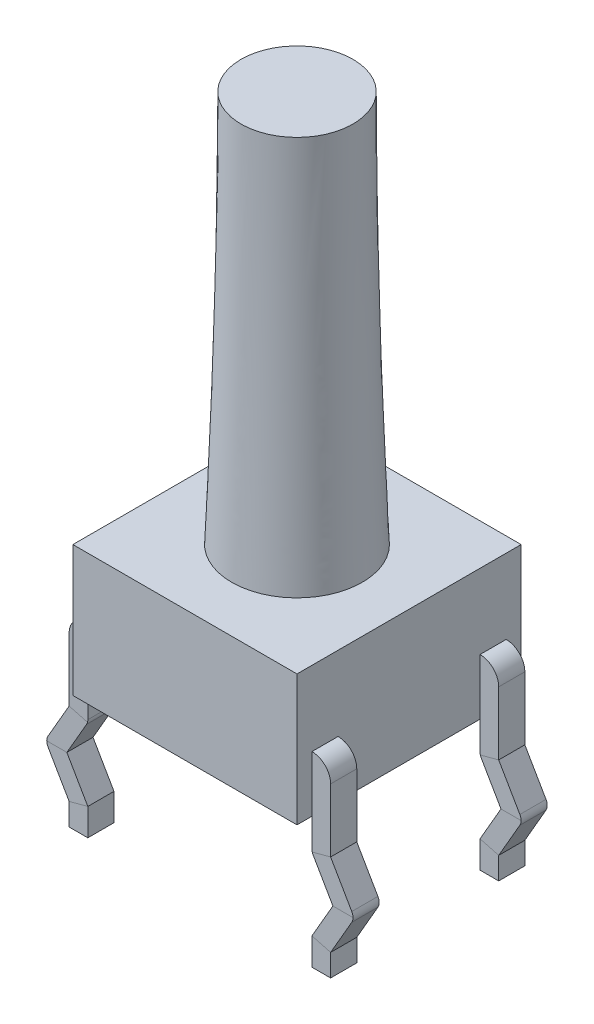
SolidWorks part; units mm, degrees
ref_plane "Front Plane" through (0, 0, 0) normal (0, 0, 1) x (1, 0, 0)
ref_plane "Top Plane" through (0, 0, 0) normal (0, 1, 0) x (1, 0, 0)
ref_plane "Right Plane" through (0, 0, 0) normal (1, 0, 0) x (0, 0, -1)
sketch "Sketch1" plane through (0, 0, 0) normal (0, 1, 0) x (1, 0, 0)
  line L0 (-3, 3) -> (-3, 2.6) construction
  line L1 (3, 3) -> (-3, 3)
  line L2 (3, 3) -> (3, -3)
  line L3 (3, -3) -> (-3, -3)
  line L4 (-3, 3) -> (-3, -3)
  line L5 (3, 3) -> (-3, -3) construction
  line L6 (3, -3) -> (-3, 3) construction
  line L7 (0, 3) -> (0, -3) construction
  line L8 (-3, 2.6) -> (-3.5, 2.6)
  line L9 (-3, 2.6) -> (-3, 1.9)
  line L10 (-3, 1.9) -> (-3.5, 1.9)
  line L11 (-3.5, 2.6) -> (-3.5, 1.9)
  line L12 (-3, 0) -> (3, 0) construction
  line L13 (-3, -1.9) -> (-3.5, -1.9)
  line L14 (-3.5, -2.6) -> (-3.5, -1.9)
  line L15 (-3, -2.6) -> (-3.5, -2.6)
  line L16 (-3, -2.6) -> (-3, -1.9)
  line L17 (3, 1.9) -> (3.5, 1.9)
  line L18 (3.5, 2.6) -> (3.5, 1.9)
  line L19 (3, 2.6) -> (3.5, 2.6)
  line L20 (3, 2.6) -> (3, 1.9)
  line L21 (3, -2.6) -> (3, -1.9)
  line L22 (3, -2.6) -> (3.5, -2.6)
  line L23 (3.5, -2.6) -> (3.5, -1.9)
  line L24 (3, -1.9) -> (3.5, -1.9)
  point P0 (0, 0)
  point P26 (-3.25, 2.25)
  dimension "D1" = 6
  dimension "D2" = 6
  dimension "D3" = 0.4
  dimension "D4" = 0.7
  dimension "D5" = 0.5
  dimension "D6" = 0.25
  dimension "D7" = 0.35
extrude "Boss-Extrude1" add sketch "Sketch1" along normal blind 3.5 contours L1 L4 L3 L2 region at (0, 0, 0)
sketch "Sketch3" plane through (0, 3.5, 0) normal (0, 1, 0) x (1, 0, 0)
  circle A0 centre (0, 0) radius 1.75
  dimension "D1" = 3.5
ref_plane "Plane1" through (0, 14, 0) normal (0, -1, 0) x (-1, 0, 0)
sketch "Sketch5" plane through (0, 14, 0) normal (0, -1, 0) x (-1, 0, 0)
  circle A0 centre (0, 0) radius 1.5
  dimension "D1" = 3
loft "Loft1" add profiles "Sketch3", "Sketch5" connector at (-1.5522, 3.5, 0.8082) connector at (-0.8133, 14, 1.2604)
extrude "Boss-Extrude2" add sketch "Sketch1<3>" along normal blind 1.5 contours L24 L2 L22 L23 | L19 L2 L17 L18 | L8 L11 L10 L4 | L14 L13 L16 L15 region at (3.25, 0, -2.25) region at (-3.25, 0, -2.25) region at (3.25, 0, 2.25)
sketch "Sketch1<3>" plane through (0, 0, 0) normal (0, 1, 0) x (1, 0, 0) same geometry as "Sketch1"
fillet "Fillet1" radius 0.5 4 edges at (3.5, 1.5, 2.25) (3.5, 1.5, -2.25) (-3.5, 1.5, 2.25) (-3.5, 1.5, -2.25)
sketch "Sketch7" plane through (0, 0, 0) normal (0, -1, 0) x (1, 0, 0)
  line L0 (-3, 1.9) -> (-3.5, 1.9) construction
  line L1 (-3.5, 2.6) -> (-3, 2.6)
  line L2 (-3.5, 2.6) -> (-3.5, 1.9)
  line L3 (-3.5, 1.9) -> (-3, 1.9)
  line L4 (-3, 2.6) -> (-3, 1.9)
  line L5 (-3, -1.9) -> (-3, 1.9) construction
  line L7 (-3.5, -1.9) -> (-3, -1.9)
  line L8 (-3.5, -1.9) -> (-3.5, -2.6)
  line L9 (-3.5, -2.6) -> (-3, -2.6)
  line L10 (-3, -1.9) -> (-3, -2.6)
  line L11 (3.5, 2.6) -> (3, 2.6)
  line L12 (3.5, 2.6) -> (3.5, 1.9)
  line L13 (3.5, 1.9) -> (3, 1.9)
  line L14 (3, 2.6) -> (3, 1.9)
  line L15 (3.5, -1.9) -> (3, -1.9)
  line L16 (3.5, -1.9) -> (3.5, -2.6)
  line L17 (3.5, -2.6) -> (3, -2.6)
  line L18 (3, -1.9) -> (3, -2.6)
ref_plane "Plane2" through (0, 0, 2.3) normal (0, 0, 1) x (1, 0, 0)
sketch "Sketch8" plane through (0, 0, 2.3) normal (0, 0, 1) x (1, 0, 0)
  line L0 (-3.25, 0) -> (-3.25, -0.7608)
  line L1 (-3.25, -0.7608) -> (-3.85, -1.8)
  line L2 (-3.85, -1.8) -> (-3.25, -2.8392)
  line L3 (-3.25, -2.8392) -> (-3.25, -3.5)
  line L4 (0, 0) -> (0, -3.568) construction
  line L5 (3.25, 0) -> (3.25, -0.7608)
  line L6 (3.25, -0.7608) -> (3.85, -1.8)
  line L7 (3.85, -1.8) -> (3.25, -2.8392)
  line L8 (3.25, -2.8392) -> (3.25, -3.5)
  dimension "D1" = 3.5
  dimension "D2" = 7.7
  dimension "D3" = 1.8
  dimension "D4" = 1.2
  dimension "D5" = 6.5
ref_plane "Plane3" through (0, -3.5, 0) normal (0, -1, 0) x (-1, 0, 0)
sketch "Sketch10" plane through (0, -3.5, 0) normal (0, -1, 0) x (-1, 0, 0)
  line L0 (-3.5, 2.6) -> (-3, 2.6)
  line L1 (-3.5, 2.6) -> (-3.5, 1.9)
  line L2 (-3.5, 1.9) -> (-3, 1.9)
  line L3 (-3, 2.6) -> (-3, 1.9)
  line L4 (-3.5, -1.9) -> (-3, -1.9)
  line L5 (-3.5, -1.9) -> (-3.5, -2.6)
  line L6 (-3.5, -2.6) -> (-3, -2.6)
  line L7 (-3, -1.9) -> (-3, -2.6)
sweep "Sweep5" add profiles "Sketch10" path "Sketch8"
ref_plane "Plane4" through (0, 0, 0) normal (1, 0, 0) x (0, 0, -1)
mirror "Mirror1" about plane through (0, 0, 0) normal (1, 0, 0) of "Sweep5"
fillet "Fillet2" radius 0.25 8 edges at (-4.1387, -1.8, 2.25) (-4.1387, -1.8, -2.25) (-3, -0.8278, -2.25) (-3, -0.8278, 2.25) (3, -0.8278, -2.25) (3, -0.8278, 2.25) (4.1387, -1.8, -2.25) (4.1387, -1.8, 2.25)
